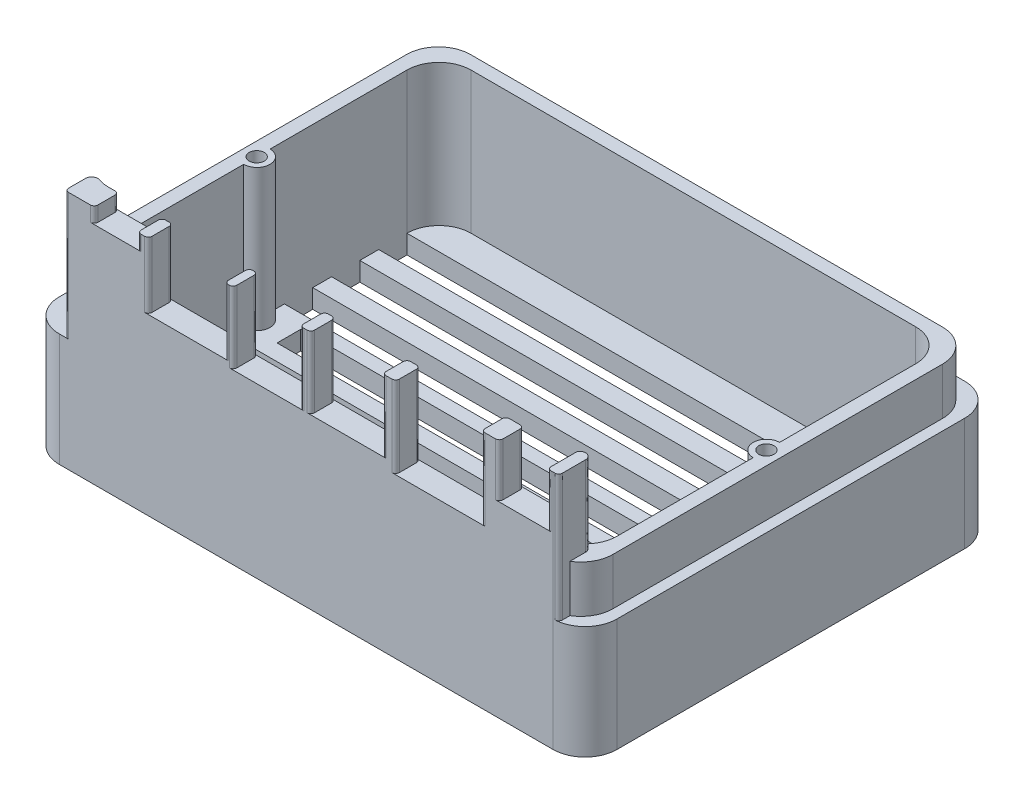
SolidWorks part; units mm, degrees
ref_plane "Front Plane" through (0, 0, 0) normal (0, 0, 1) x (1, 0, 0)
ref_plane "Top Plane" through (0, 0, 0) normal (0, 1, 0) x (1, 0, 0)
ref_plane "Right Plane" through (0, 0, 0) normal (1, 0, 0) x (0, 0, -1)
sketch "Sketch1" plane through (0, 0, 0) normal (0, 1, 0) x (1, 0, 0)
  line L1 (59.2, -43.7) -> (-59.2, -43.7)
  line L2 (59.2, -43.7) -> (59.2, 43.7)
  line L3 (59.2, 43.7) -> (-59.2, 43.7)
  line L4 (-59.2, -43.7) -> (-59.2, 43.7)
  line L5 (59.2, -43.7) -> (-59.2, 43.7) construction
  line L6 (59.2, 43.7) -> (-59.2, -43.7) construction
  point P0 (0, 0)
  dimension "D1" = 118.4
  dimension "D2" = 87.4
extrude "Boss-Extrude1" add sketch "Sketch1" along normal blind 51
sketch "Sketch2" plane through (0, 51, 0) normal (0, 1, 0) x (1, 0, 0)
  line L0 (-59.2, 0) -> (-54.2, 0) construction
  line L1 (-59.2, 43.7) -> (-59.2, -43.7) construction
  line L2 (59.2, 0) -> (54.2, 0) construction
  line L3 (59.2, -43.7) -> (59.2, 43.7) construction
  line L4 (0, 43.7) -> (0, 38.7) construction
  line L5 (59.2, 43.7) -> (-59.2, 43.7) construction
  line L6 (0, -43.7) -> (0, -38.7) construction
  line L7 (-59.2, -43.7) -> (59.2, -43.7) construction
  line L9 (-54, 38.5) -> (54, 38.5)
  line L10 (-54, 38.5) -> (-54, -38.5)
  line L11 (-54, -38.5) -> (54, -38.5)
  line L12 (54, 38.5) -> (54, -38.5)
  dimension "D1" = 5
  dimension "D2" = 5
  dimension "D3" = 5
  dimension "D4" = 5
extrude "Cut-Extrude1" cut sketch "Sketch2" against normal blind 47
sketch "Sketch3" plane through (-59.2, 0, 0) normal (-1, 0, 0) x (0, 0, 1)
  line L0 (0, 51) -> (0, 34) construction
  line L1 (-43.7, 51) -> (43.7, 51) construction
  line L2 (-43.7, 34) -> (38.5, 34)
  line L3 (-43.7, 51) -> (-43.7, 0) construction
  line L4 (-43.7, 34) -> (-43.7, 51)
  line L5 (-43.7, 51) -> (38.5, 51)
  line L6 (38.5, 51) -> (38.5, 34)
  dimension "D1" = 17
  dimension "D2" = 82.2
extrude "Cut-Extrude2" cut sketch "Sketch3" against normal through all
sketch "Sketch4" plane through (0, 0, -43.7) normal (0, 0, -1) x (-1, 0, 0)
  line L5 (59.2, 34) -> (59.2, 0) construction
  line L6 (-59.2, 34) -> (59.2, 34)
  line L7 (-59.2, 34) -> (-59.2, 24)
  line L8 (-59.2, 24) -> (59.2, 24)
  line L9 (59.2, 34) -> (59.2, 24)
  dimension "D1" = 10
extrude "Cut-Extrude4" cut sketch "Sketch4" against normal blind 2.4
sketch "Sketch5" plane through (0, 0, 38.5) normal (0, 0, -1) x (-1, 0, 0)
  line L0 (59.2, 34) -> (-59.2, 34) construction
  line L1 (-59.2, 51) -> (-53.6, 51)
  line L2 (-59.2, 51) -> (-59.2, 34)
  line L3 (-59.2, 34) -> (-53.6, 34)
  line L4 (-53.6, 51) -> (-53.6, 34)
  line L5 (-53.6, 51) -> (-51.2, 51) construction
  line L6 (59.2, 51) -> (51.2, 51)
  line L7 (59.2, 51) -> (59.2, 34)
  line L8 (59.2, 34) -> (51.2, 34)
  line L9 (51.2, 51) -> (51.2, 34)
  line L10 (59.2, 51) -> (-59.2, 51) construction
  line L11 (-51.2, 51) -> (-51.2, 39.8)
  line L12 (-51.2, 39.8) -> (-41, 39.8)
  line L13 (-41, 39.8) -> (-41, 51)
  line L14 (-51.2, 51) -> (-41, 51)
  line L15 (-37.2, 51) -> (-37.2, 33.8)
  line L16 (-37.2, 33.8) -> (-19, 33.8)
  line L17 (-19, 33.8) -> (-19, 51)
  line L18 (-37.2, 51) -> (-19, 51)
  line L19 (-16.2, 51) -> (-16.2, 35.8)
  line L20 (-16.2, 35.8) -> (-1, 35.8)
  line L21 (-1, 35.8) -> (-1, 51)
  line L22 (-16.2, 51) -> (-1, 51)
  line L23 (-1, 51) -> (1.3, 51) construction
  line L24 (1.3, 51) -> (1.3, 35.8)
  line L25 (1.3, 35.8) -> (15.5, 35.8)
  line L26 (15.5, 35.8) -> (15.5, 51)
  line L27 (15.5, 51) -> (1.3, 51)
  line L28 (15.5, 51) -> (17.3, 51) construction
  line L29 (17.3, 51) -> (17.3, 37)
  line L30 (17.3, 37) -> (33.5, 37)
  line L31 (33.5, 37) -> (33.5, 51)
  line L32 (17.3, 51) -> (33.5, 51)
  line L33 (35.8, 51) -> (35.8, 47.8)
  line L34 (35.8, 47.8) -> (45, 47.8)
  line L35 (45, 47.8) -> (45, 51)
  line L36 (45, 51) -> (35.8, 51)
  dimension "D1" = 5.6
  dimension "D2" = 8
  dimension "D4" = 11.2
  dimension "D5" = 10.2
  dimension "D6" = 3.8
  dimension "D7" = 18.2
  dimension "D8" = 2.8
  dimension "D9" = 15.2
  dimension "D10" = 15.2
  dimension "D11" = 2.3
  dimension "D12" = 14.2
  dimension "D13" = 1.8
  dimension "D14" = 14
  dimension "D15" = 16.2
  dimension "D16" = 2.3
  dimension "D17" = 3.2
  dimension "D18" = 9.2
  dimension "D19" = 17.2
  dimension "D20" = 15.2
extrude "Cut-Extrude5" cut sketch "Sketch5" against normal up to next
sketch "Sketch6" plane through (59.2, 0, 0) normal (1, 0, 0) x (0, 0, -1)
  line L1 (-43.7, 34) -> (41.3, 34)
  line L2 (-43.7, 34) -> (-43.7, 24)
  line L3 (-43.7, 24) -> (41.3, 24)
  line L4 (41.3, 34) -> (41.3, 24)
extrude "Cut-Extrude6" cut sketch "Sketch6" against normal blind 2.3
sketch "Sketch7" plane through (-59.2, 0, 0) normal (-1, 0, 0) x (0, 0, 1)
  line L1 (-41.3, 34) -> (43.7, 34)
  line L2 (-41.3, 34) -> (-41.3, 24)
  line L3 (-41.3, 24) -> (43.7, 24)
  line L4 (43.7, 34) -> (43.7, 24)
extrude "Cut-Extrude7" cut sketch "Sketch7" against normal blind 2.3
sketch "Sketch8" plane through (0, 0, 43.7) normal (0, 0, 1) x (1, 0, 0)
  line L0 (-51.2, 34) -> (-51.2, 19.6122) construction
  line L1 (-56.9, 24) -> (56.9, 24) construction
  line L2 (53.6, 34) -> (53.6, 19.6122) construction
  line L4 (-56.9, 34) -> (-51.2, 34)
  line L5 (-56.9, 34) -> (-56.9, 24)
  line L6 (-56.9, 24) -> (-51.2, 24)
  line L7 (-51.2, 34) -> (-51.2, 24)
  line L8 (56.9, 34) -> (53.6, 34)
  line L9 (56.9, 34) -> (56.9, 24)
  line L10 (56.9, 24) -> (53.6, 24)
  line L11 (53.6, 34) -> (53.6, 24)
extrude "Cut-Extrude8" cut sketch "Sketch8" against normal blind 2.4
fillet "Fillet1" radius 6.8 12 edges at (54, 19, -38.5) (54, 19, 38.5) (-54, 19, -38.5) (-54, 19, 38.5) (-59.2, 12, 43.7) (-56.9, 29, 41.3) (-59.2, 12, -43.7) (-56.9, 29, -41.3) (59.2, 12, -43.7) (56.9, 29, -41.3) (56.9, 29, 41.3) (59.2, 12, 43.7) first distance on face at (54, 19, 0) first distance on face at (1.225, 41.1875, 38.5) first distance on face at (0, 19, -38.5) first distance on face at (-54, 19, 0) first distance on face at (1.225, 39.6875, 43.7) first distance on face at (-56.9, 29, 0) first distance on face at (0, 12, -43.7) first distance on face at (0, 29, -41.3) first distance on face at (56.9, 29, 0)
fillet "Fillet2" radius 0.8 26 edges at (-35.8, 49.4, 38.5) (-33.5, 44, 38.5) (-33.5, 44, 43.7) (-45, 49.4, 38.5) (-35.8, 49.4, 43.7) (-45, 49.4, 43.7) (-51.2, 37.5, 43.7) (-15.5, 43.4, 43.7) (-17.3, 44, 43.7) (-17.3, 44, 38.5) (-15.5, 43.4, 38.5) (-1.3, 43.4, 38.5) (1, 43.4, 38.5) (-1.3, 43.4, 43.7) (1, 43.4, 43.7) (19, 42.4, 43.7) (19, 42.4, 38.5) (16.2, 43.4, 38.5) (16.2, 43.4, 43.7) (37.2, 42.4, 43.7) (37.2, 42.4, 38.5) (41, 45.4, 38.5) (41, 45.4, 43.7) (51.2, 45.4, 43.7) (51.2, 45.4, 37.1991) (53.6, 37.5, 43.5933) first distance on face at (-2.6154, 41.3231, 38.5) first distance on face at (-2.2667, 40.2833, 43.7) first distance on face at (51.6351, 32.5625, 35.5383) first distance on face at (55.4714, 22.75, 41.7364)
sketch "Sketch9" plane through (0, 4, 0) normal (0, 1, 0) x (1, 0, 0)
  line L2 (-54, 31.7) -> (-54, -31.7) construction
  line L3 (-54, 2.6446) -> (-54, -2.9554)
  line L7 (-51.2, -0.0104) -> (-51.2, -0.1554) construction
  line L9 (54, 2.8) -> (54, -2.8)
  line L15 (54, -31.7) -> (54, 31.7) construction
  line L16 (-51.2, -0.0104) -> (-51.2038, -0.0104) construction
  arc A3 (-54, -2.9554) -> (-54, 2.6446) centre (-54, -0.1554) ccw
  arc A4 (54, 2.8) -> (54, -2.8) centre (54, 0) ccw
  point P23 (54, 0)
  line M6 (54, -31.7) -> (54, 31.7)
  line M10 (-54, 31.7) -> (-54, -31.7)
  dimension "D1" = 2.8
  dimension "D2" = 2.8
extrude "Boss-Extrude2" add sketch "Sketch9" along normal blind 30 contours A4 M6 | A3 M10 region at (-52.8116, 4, 0.1554) region at (52.8116, 4, 0)
sketch "Sketch10" plane through (0, 4, 0) normal (0, 1, 0) x (1, 0, 0)
  line L2 (-54, 2.6446) -> (-54, -3.023) construction
  line L3 (-54, -2.9554) -> (-54, -31.7) construction
  line L4 (54, 2.8) -> (54, -2.8) construction
  line L5 (-59.2, 0) -> (59.2, 0) construction
  line L6 (-59.2, -36.9) -> (-59.2, 36.9) construction
  line L7 (59.2, -36.9) -> (59.2, 36.9) construction
  circle A3 centre (-54, -0.1892) radius 1.6
  circle A4 centre (54, 0) radius 1.6
  dimension "D1" = 3.2
  dimension "D2" = 3.2
extrude "Cut-Extrude9" cut sketch "Sketch10" along normal through all both and the other way through all
sketch "Sketch11" plane through (0, 0, 0) normal (0, -1, 0) x (1, 0, 0)
  circle A0 centre (-54, 0.1892) radius 3.5
  circle A1 centre (54, 0) radius 3.5
  dimension "D1" = 7
  dimension "D2" = 7
extrude "Cut-Extrude10" cut sketch "Sketch11" against normal blind 2
sketch "Sketch12" plane through (0, 4, 0) normal (0, 1, 0) x (1, 0, 0)
  line L0 (54, 2.8) -> (54, 31.7) construction
  line L1 (-54, 31.7) -> (54, 31.7)
  line L2 (-54, 31.7) -> (-54, 25.7)
  line L3 (-54, 25.7) -> (54, 25.7)
  line L4 (54, 31.7) -> (54, 25.7)
  line L5 (54, 25.7) -> (54, 21.7) construction
  line L6 (54, 2.8) -> (54, 31.7) construction
  line L7 (-54, 31.7) -> (-54, 2.6446) construction
  line L8 (54, 21.7) -> (-54, 21.7)
  line L9 (54, 21.7) -> (54, 15.7)
  line L10 (54, 15.7) -> (-54, 15.7)
  line L11 (-54, 21.7) -> (-54, 15.7)
  line L12 (-54, 15.7) -> (-54, 11.7) construction
  line L13 (-54, 5.7) -> (-54, 2.6446) construction
  line L14 (-54, 11.7) -> (54, 11.7)
  line L15 (-54, 11.7) -> (-54, 5.7)
  line L16 (-54, 5.7) -> (54, 5.7)
  line L17 (54, 11.7) -> (54, 5.7)
  line L18 (-54, -2.9554) -> (-54, -9.8154) construction
  line L19 (-54, -2.9554) -> (-54, -31.7) construction
  line L20 (54, -31.7) -> (54, -2.8) construction
  line L21 (-54, -5.7) -> (54, -5.7)
  line L22 (-54, -5.7) -> (-54, -11.7)
  line L23 (-54, -11.7) -> (54, -11.7)
  line L24 (54, -5.7) -> (54, -11.7)
  line L25 (-54, -11.7) -> (-54, -15.7) construction
  line L26 (54, -31.7) -> (54, -2.8) construction
  line L27 (-54, -15.7) -> (54, -15.7)
  line L28 (-54, -15.7) -> (-54, -21.7)
  line L29 (-54, -21.7) -> (54, -21.7)
  line L30 (54, -15.7) -> (54, -21.7)
  line L31 (54, -21.7) -> (54, -25.7) construction
  line L33 (54, -25.7) -> (-54, -25.7)
  line L34 (54, -25.7) -> (54, -31.7)
  line L35 (54, -31.7) -> (-54, -31.7)
  line L36 (-54, -25.7) -> (-54, -31.7)
  line L37 (-47.6148, 2.7484) -> (47.5832, 2.7484)
  line L38 (-47.6148, 2.7484) -> (-47.6148, -2.2516)
  line L39 (-47.6148, -2.2516) -> (47.5832, -2.2516)
  line L40 (47.5832, 2.7484) -> (47.5832, -2.2516)
  dimension "D1" = 6
  dimension "D2" = 4
  dimension "D3" = 6
  dimension "D4" = 4
  dimension "D5" = 6
  dimension "D6" = 6.86
  dimension "D7" = 6
  dimension "D8" = 4
  dimension "D9" = 6
  dimension "D10" = 4
  dimension "D11" = 6
  dimension "D12" = 5
extrude "Cut-Extrude11" cut sketch "Sketch12" against normal blind 10
fillet "Fillet3" radius 1.3 2 edges at (53.6, 42.5, 33.9978) (-51.2, 42.5, 37.1991) first distance on face at (51.9277, 31.8625, 35.3832) first distance on face at (-51.1926, 28.25, 36.1715)
